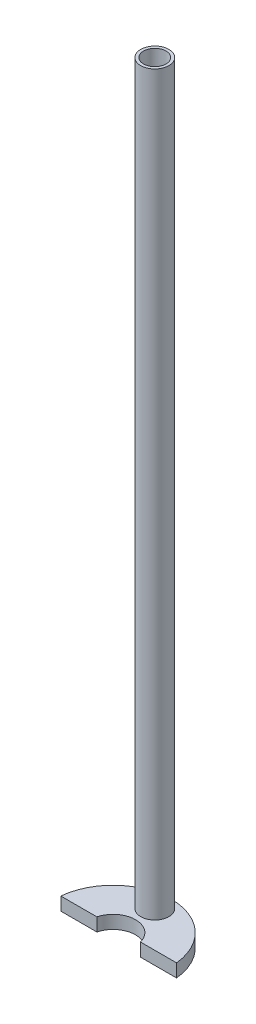
SolidWorks part; units mm, degrees
ref_plane "Front Plane" through (0, 0, 0) normal (0, 0, 1) x (1, 0, 0)
ref_plane "Top Plane" through (0, 0, 0) normal (0, 1, 0) x (1, 0, 0)
ref_plane "Right Plane" through (0, 0, 0) normal (1, 0, 0) x (0, 0, -1)
sketch "Sketch2" plane through (0, 0, 0) normal (0, 1, 0) x (1, 0, 0)
  line L0 (-15.5, 0) -> (15.5, 0) construction
  line L1 (-15.4272, -1.5) -> (15.4272, -1.5)
  line L2 (-15.4272, 1.5) -> (15.4272, 1.5)
  line L3 (0, 6.25) -> (0, 11.125) construction
  circle A0 centre (0, 0) radius 15.5
  circle A1 centre (0, 0) radius 6.25 construction
  circle A2 centre (0, 11.125) radius 3.75
  circle A3 centre (0, 0) radius 6
  dimension "D1" = 31
  dimension "D2" = 12.5
  dimension "D5" = 7.5
  dimension "D6" = 12
  dimension "D3" = 1.5
  dimension "D4" = 4.875
extrude "Boss-Extrude1" add sketch "Sketch2" along normal blind 3.5 contours A3 L2 A0 A2 | A2 region at (0, 0, -7.3601) region at (0, 0, -11.125)
extrude "Boss-Extrude2" add sketch "Sketch2<5>" along normal blind 200 contours A2
sketch "Sketch2<5>" plane through (0, 0, 0) normal (0, 1, 0) x (1, 0, 0) same geometry as "Sketch2"
sketch "Sketch3" plane through (0, 200, 0) normal (0, 1, 0) x (1, 0, 0)
  circle A0 centre (0, 11.125) radius 3
  dimension "D1" = 6
extrude "Cut-Extrude1" cut sketch "Sketch3" against normal through all
